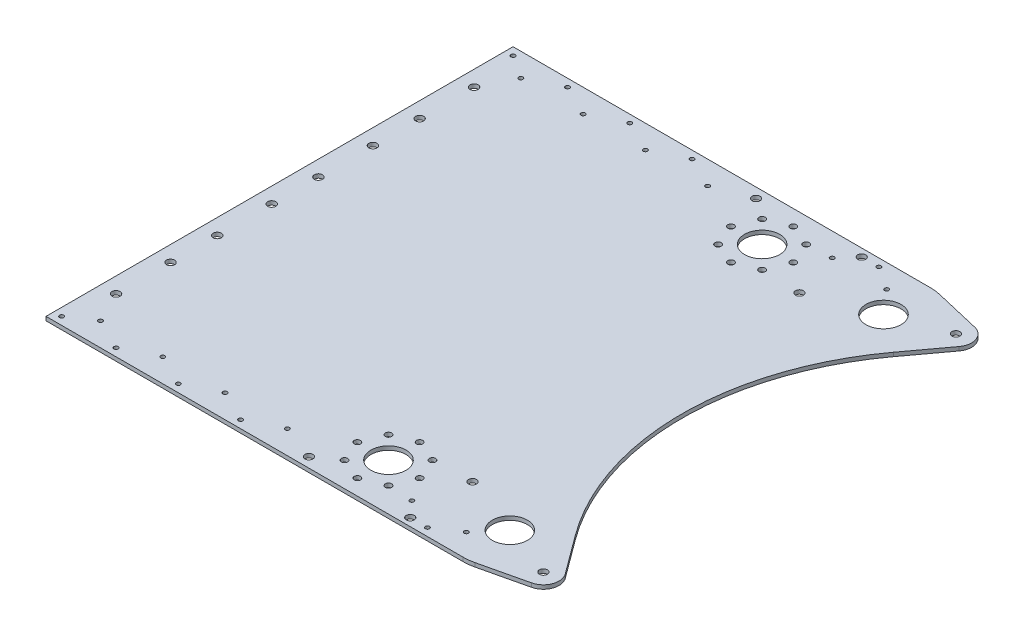
SolidWorks part; units mm, degrees
material "6061-T6 (SS)"
ref_plane "Front Plane" through (0, 0, 0) normal (0, 0, 1) x (1, 0, 0)
ref_plane "Top Plane" through (0, 0, 0) normal (0, 1, 0) x (1, 0, 0)
ref_plane "Right Plane" through (0, 0, 0) normal (1, 0, 0) x (0, 0, -1)
sketch "Sketch1" plane through (0, 0, 0) normal (0, 1, 0) x (1, 0, 0)
  line L1 (215.9, -190.5) -> (-215.9, -190.5)
  line L2 (215.9, -190.5) -> (215.9, 190.5)
  line L3 (215.9, 190.5) -> (-215.9, 190.5)
  line L4 (-215.9, -190.5) -> (-215.9, 190.5)
  line L5 (215.9, -190.5) -> (-215.9, 190.5) construction
  line L6 (215.9, 190.5) -> (-215.9, -190.5) construction
  point P0 (0, 0)
  dimension "D1" = 431.8
  dimension "D2" = 381
extrude "Boss-Extrude1" add sketch "Sketch1" along normal blind 3.175
sketch "Sketch6" plane through (0, 3.175, 0) normal (0, 1, 0) x (1, 0, 0)
  line L1 (25.4, 152.4) -> (0, 0) construction
  line L2 (0, 0) -> (25.4, -152.4) construction
  line L5 (-215.9, 190.5) -> (-215.9, -190.5) construction
  circle A0 centre (25.4, -152.4) radius 38.1 construction
  circle A1 centre (25.4, 152.4) radius 38.1 construction
  circle A2 centre (124.4092, -152.4) radius 38.1 construction
  circle A3 centre (124.4092, 152.4) radius 38.1 construction
  dimension "D1" = 76.2
  dimension "D5" = 228.6
  dimension "D3" = 99.0092
  dimension "D4" = 241.3
sketch "Sketch7" plane through (0, 3.175, 0) normal (0, 1, 0) x (1, 0, 0)
  circle A0 centre (124.4092, -152.4) radius 14.3129
  circle A1 centre (124.4092, 152.4) radius 14.3129
  circle A2 centre (25.4, 152.4) radius 14.3129
  circle A3 centre (25.4, -152.4) radius 14.3129
  circle A4 centre (0, 152.4) radius 2.5527
  circle A5 centre (25.4, 152.4) radius 25.4 construction
  circle A6 centre (7.4395, 170.3605) radius 2.5527
  circle A7 centre (25.4, 177.8) radius 2.5527
  circle A8 centre (43.3605, 170.3605) radius 2.5527
  circle A9 centre (25.4, -152.4) radius 25.4 construction
  circle A10 centre (25.4, -127) radius 2.5527
  circle A11 centre (43.3605, -134.4395) radius 2.5527
  circle A12 centre (50.8, -152.4) radius 2.5527
  circle A13 centre (43.3605, -170.3605) radius 2.5527
  circle A14 centre (50.8, 152.4) radius 2.5527
  circle A15 centre (43.3605, 134.4395) radius 2.5527
  circle A16 centre (25.4, 127) radius 2.5527
  circle A17 centre (7.4395, 134.4395) radius 2.5527
  circle A18 centre (25.4, -177.8) radius 2.5527
  circle A19 centre (7.4395, -170.3605) radius 2.5527
  circle A20 centre (0, -152.4) radius 2.5527
  circle A21 centre (7.4395, -134.4395) radius 2.5527
  point P24 (25.4, 152.4)
  point P34 (25.4, -152.4)
  dimension "D1" = 28.6258
  dimension "D2" = 28.6258
  dimension "D3" = 5.1054
  dimension "D5" = 50.8
  dimension "D4" = 8
  dimension "D6" = 8
extrude "Axle Holes" cut sketch "Sketch7" against normal through all
sketch "Sketch10" plane through (0, 3.175, 0) normal (0, 1, 0) x (1, 0, 0)
  line L0 (0, 0) -> (57.9248, 0) construction
  circle A0 centre (-9.525, -182.3949) radius 3.2385
  circle A1 centre (74.9046, -184.15) radius 3.2385
  circle A2 centre (74.9046, -133.35) radius 2.5527 construction
  circle A3 centre (74.9046, -133.35) radius 3.2385
  circle A4 centre (167.623, -168.275) radius 3.2385
  circle A10 centre (-9.525, -182.3949) radius 2.5527 construction
  circle A11 centre (74.9046, -184.15) radius 2.5527 construction
  circle A12 centre (167.623, -168.275) radius 2.5527 construction
  circle A13 centre (74.9046, -133.35) radius 2.5527 construction
  circle A14 centre (-9.525, -182.3949) radius 2.5527 construction
  circle A15 centre (74.9046, -184.15) radius 2.5527 construction
  circle A16 centre (167.623, -168.275) radius 2.5527 construction
  circle A17 centre (167.623, 168.275) radius 3.2385
  circle A18 centre (74.9046, 184.15) radius 3.2385
  circle A19 centre (74.9046, 133.35) radius 3.2385
  circle A20 centre (-9.525, 182.3949) radius 3.2385
  dimension "D1" = 6.477
extrude "Cut-Extrude5" cut sketch "Sketch10" against normal through all
sketch "Sketch8" plane through (0, 3.175, 0) normal (0, 1, 0) x (1, 0, 0)
  line L0 (155.0606, -129.7704) -> (177.8913, -160.6941)
  line L1 (133.1219, -189.4904) -> (170.5418, -180.7003)
  line L5 (0, 0) -> (-35.0112, 0) construction
  line L6 (155.0606, 129.7704) -> (177.8913, 160.6941)
  line L7 (133.1219, 189.4904) -> (170.5418, 180.7003)
  circle A4 centre (124.4092, -152.4) radius 38.1 construction
  circle A5 centre (167.623, -168.275) radius 12.7635 construction
  arc A7 (170.5418, -180.7003) -> (177.8913, -160.6941) centre (167.623, -168.275) ccw
  arc A8 (155.0606, -129.7704) -> (155.0606, 129.7704) centre (330.8323, 0) cw
  circle A9 centre (167.623, -168.275) radius 3.2385 construction
  arc A10 (170.5418, 180.7003) -> (177.8913, 160.6941) centre (167.623, 168.275) cw
  arc A11 (133.1219, -189.4904) -> (124.4092, -190.5) centre (124.4092, -152.4) cw
  arc A12 (133.1219, 189.4904) -> (124.4092, 190.5) centre (124.4092, 152.4) ccw
  dimension "D2" = 9.525
  dimension "D1" = 76.2
extrude "Cut-Extrude4" cut sketch "Sketch8" against normal through all flip side to cut
hole_wizard "1/4 (0.26) Diameter Hole1" positions "Sketch11" profile "Sketch12" hole size "1/4" standard "ANSI Inch" end condition through all
sketch "Sketch11" plane through (0, 3.175, 0) normal (0, 1, 0) x (1, 0, 0)
  line L0 (-203.2, -101.6) -> (-203.2, -146.05) construction
  line L2 (-215.9, -190.5) -> (124.4092, -190.5) construction
  line L3 (-203.2, 146.05) -> (-203.2, 101.6) construction
  line L6 (-203.2, -146.05) -> (-203.2, -190.5) construction
  line L8 (-203.2, 146.05) -> (-203.2, 190.5) construction
  line L9 (124.4092, 190.5) -> (-215.9, 190.5) construction
  line L11 (-215.9, 190.5) -> (-215.9, -190.5) construction
  point P0 (-203.2, -146.05)
  point P2 (-203.2, -101.6)
  point P16 (-203.2, -63.5)
  point P17 (-203.2, -19.05)
  point P18 (-203.2, 19.05)
  point P19 (-203.2, 63.5)
  point P20 (-203.2, 101.6)
  point P21 (-203.2, 146.05)
  dimension "D1" = 44.45
  dimension "D2" = 82.55
  dimension "D4" = 12.7
  dimension "D3" = 4
sketch "Sketch12" plane through (-203.2, 3.175, 146.05) normal (1, 0, 0) x (0, 0, 1)
  line L0 (0, 0) -> (0, 3.175)
  line L1 (0, 3.175) -> (3.302, 3.175)
  line L2 (3.302, 3.175) -> (3.302, 0)
  line L5 (3.302, 0) -> (0, 0)
  line L11 (0, -6.35) -> (0, 107.95) construction
  dimension "Thru Hole Dia." = 6.604
  dimension "Thru Hole Depth" = 3.175
hole_wizard "1/8 (0.135) Diameter Hole1" positions "Sketch13" profile "Sketch14" hole size "1/8" standard "ANSI Inch" end condition up to next
sketch "Sketch13" plane through (0, 3.175, 0) normal (0, 1, 0) x (1, 0, 0)
  point P0 (-190.5, -171.45)
  point P3 (-165.1, -184.15)
  point P6 (-139.7, -171.45)
  point P9 (-114.3, -184.15)
  point P12 (-88.9, -171.45)
  point P15 (-63.5, -184.15)
  point P18 (-38.1, -171.45)
  point P24 (63.5, -171.45)
  point P27 (88.9, -184.15)
  point P31 (88.9, 184.15)
  point P34 (63.5, 171.45)
  point P37 (-38.1, 171.45)
  point P40 (-63.5, 184.15)
  point P43 (-88.9, 171.45)
  point P46 (-114.3, 184.15)
  point P49 (-139.7, 171.45)
  point P52 (-165.1, 184.15)
  point P55 (-190.5, 171.45)
  point P59 (-209.55, -184.15)
  point P62 (107.95, -171.45)
  point P66 (107.95, 171.45)
  point P69 (-209.55, 184.15)
sketch "Sketch14" plane through (-190.5, 3.175, 171.45) normal (1, 0, 0) x (0, 0, 1)
  line L0 (0, 0) -> (0, 3.175)
  line L1 (0, 3.175) -> (1.7145, 3.175)
  line L2 (1.7145, 3.175) -> (1.7145, 0)
  line L5 (1.7145, 0) -> (0, 0)
  line L11 (0, -6.35) -> (0, 107.95) construction
  dimension "Thru Hole Dia." = 3.429
  dimension "Thru Hole Depth" = 3.175
